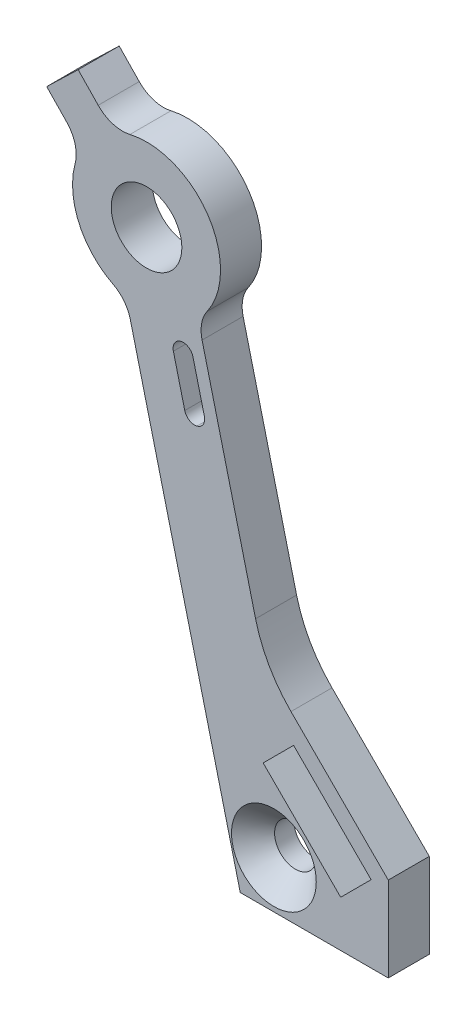
SolidWorks part; units mm, degrees
ref_plane "Front Plane" through (0, 0, 0) normal (0, 0, 1) x (1, 0, 0)
ref_plane "Top Plane" through (0, 0, 0) normal (0, 1, 0) x (1, 0, 0)
ref_plane "Right Plane" through (0, 0, 0) normal (1, 0, 0) x (0, 0, -1)
sketch "Sketch1" plane through (0, 0, 0) normal (0, 0, 1) x (1, 0, 0)
  line L0 (0, 11) -> (11, 0) construction
  line L1 (0, 0) -> (11, 0)
  line L2 (0, 0) -> (0, 11) construction
  line L3 (0, 11) -> (11, 11) construction
  line L4 (11, 0) -> (11, 11) construction
  line L5 (0, 0) -> (2.5, 0)
  line L6 (0, 0) -> (0, 3.5)
  line L7 (0, 3.5) -> (2.5, 3.5) construction
  line L8 (2.5, 0) -> (2.5, 3.5) construction
  line L9 (10.8939, 0) -> (10.947, 0.053) construction
  line L10 (7.4645, 3.4295) -> (1.7015, 9.1924)
  line L11 (1.7015, 9.1924) -> (3.9643, 11.4551)
  line L12 (7.4645, 3.4295) -> (9.7272, 5.6922)
  line L13 (3.9643, 11.4551) -> (9.7272, 5.6922)
  line L14 (0, 0) -> (-9.6331, 38.6679)
  line L15 (-9.6331, 38.6679) -> (-4.2962, 39.9974)
  line L16 (-4.2962, 39.9974) -> (1.8076, 15.4963)
  line L17 (1.8076, 15.4963) -> (11, 6.3039)
  line L18 (11, 0) -> (7.5175, 3.4825)
  line L19 (11, 6.3039) -> (11, 0)
  line L20 (0, 0) -> (0, 40.9886) construction
  line L21 (-6.9646, 39.3327) -> (-13.2153, 45.8079) construction
  line L22 (-14.3845, 44.6793) -> (-12.0462, 46.9365)
  line L23 (-12.0462, 46.9365) -> (-9.4448, 44.2417) construction
  line L24 (-14.3845, 44.6793) -> (-11.7831, 41.9845)
  line L25 (-12.0462, 46.9365) -> (-9.4448, 44.2417)
  line L27 (-5.1508, 33.0859) -> (-3.9421, 28.2342)
  line L28 (-3.9421, 28.2342) -> (-2.4866, 28.5968)
  line L29 (-2.4866, 28.5968) -> (-3.6953, 33.4485)
  line L30 (-3.6953, 33.4485) -> (-5.1508, 33.0859)
  line L31 (-7.4575, 29.9348) -> (-4.5464, 30.66) construction
  circle A0 centre (2.5, 3.5) radius 1.5
  circle A1 centre (-6.9646, 39.3327) radius 2.625
  circle A3 centre (-6.9646, 39.3327) radius 5.5
  point P28 (-13.2153, 45.8079)
  dimension "D5" = 3
  dimension "D6" = 5.25
  dimension "D7" = 11
  dimension "D1" = 11
  dimension "D2" = 11
  dimension "D3" = 3.5
  dimension "D4" = 2.5
  dimension "D8" = 45
  dimension "D9" = 6.3039
  dimension "D10" = 90
  dimension "D11" = 90
  dimension "D12" = 25.25
  dimension "D13" = 13
  dimension "D14" = 3.2
  dimension "D15" = 8.15
  dimension "D16" = 0.075
  dimension "D17" = 4.925
  dimension "D18" = 5.5
  dimension "D19" = 90
  dimension "D20" = 3.25
  dimension "D21" = 90
  dimension "D22" = 90
  dimension "D23" = 9
  dimension "D24" = 150
  dimension "D25" = 9
  dimension "D32" = 5
  dimension "D33" = 1.5
  dimension "D34" = 3
extrude "Boss-Extrude1" add sketch "Sketch1" along normal blind 3.05 contours A3 L14 L15 A1 L16 | L14 A3 L16 L15 A1 | A3 L14 L1 L12 L10 L11 L13 L19 L17 L16 A0 | L25 L22 L24 A3 | L24 A3 | A3 L14 region at (0.3238, 14.731, 0) region at (-11.9007, 37.2799, 0) region at (-6.1079, 35.8937, 0) region at (-11.9712, 44.5191, 0)
hole_wizard "CSK for M3 Flat Head Machine Screw1" positions "Sketch2" profile "Sketch3" countersink size "M3" standard "ANSI Metric" end condition through all
sketch "Sketch2" plane through (0, 0, 3.05) normal (0, 0, 1) x (1, 0, 0)
  point P0 (2.5, 3.5)
sketch "Sketch3" plane through (2.5, 3.5, 3.05) normal (1, 0, 0) x (0, -1, 0)
  line L0 (0, 0) -> (0, 3.05)
  line L1 (0, 3.05) -> (1.55, 3.05)
  line L2 (1.55, 3.05) -> (1.55, 1.6)
  line L3 (1.55, 1.6) -> (3.15, 0)
  line L5 (3.15, 0) -> (0, 0)
  line L6 (-1.55, 1.6) -> (-3.15, 0) construction
  line L11 (0, -6.35) -> (0, 107.95) construction
  dimension "Thru Hole Dia." = 3.1
  dimension "Thru Hole Depth" = 3.05
  dimension "Near C'Sink Dia." = 6.3
  dimension "Near C'Sink Angle" = 90
fillet "Fillet3" radius 2.5 4 edges at (-9.4448, 44.2417, 1.525) (-11.7831, 41.9845, 1.525) (-8.4817, 34.046, 1.525) (-3.1448, 35.3756, 1.525)
fillet "Fillet4" radius 10 1 edges at (1.8076, 15.4963, 1.525)
fillet "Fillet6" radius 0.75 4 edges at (-2.4866, 28.5968, 1.525) (-3.9421, 28.2342, 1.525) (-3.6953, 33.4485, 1.525) (-5.1508, 33.0859, 1.525)
